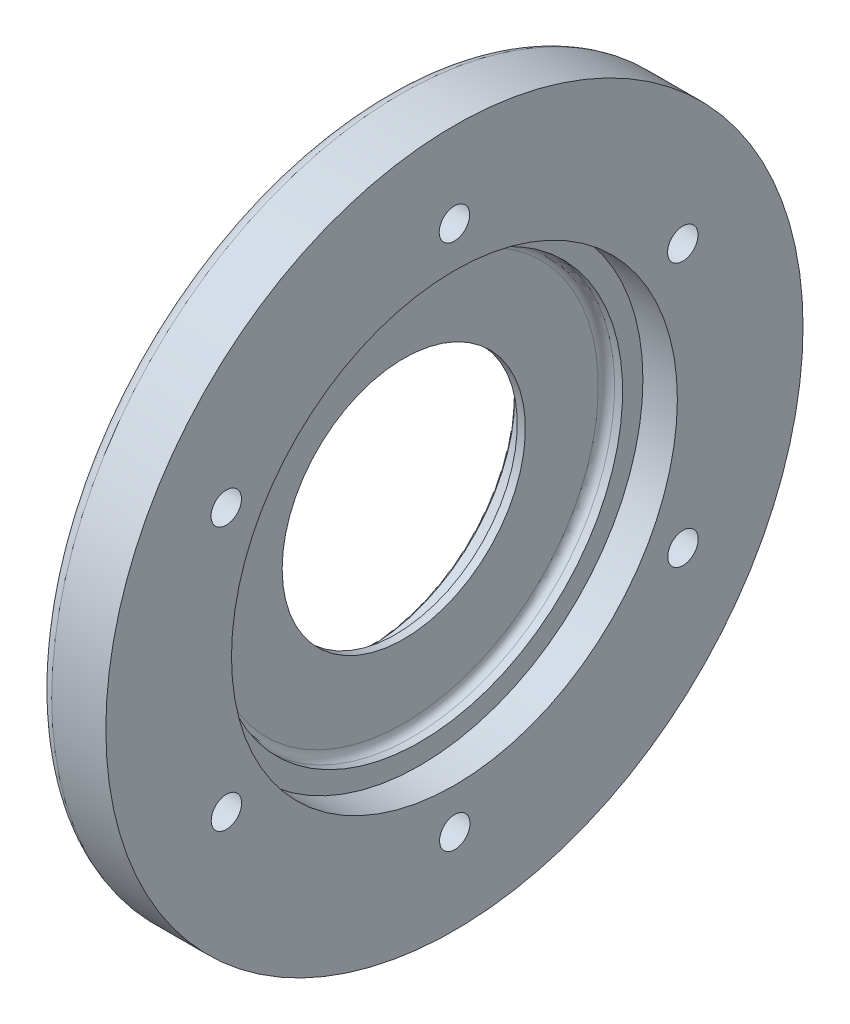
SolidWorks part; units mm, degrees
ref_plane "Front Plane" through (0, 0, 0) normal (0, 0, 1) x (1, 0, 0)
ref_plane "Top Plane" through (0, 0, 0) normal (0, 1, 0) x (1, 0, 0)
ref_plane "Right Plane" through (0, 0, 0) normal (1, 0, 0) x (0, 0, -1)
sketch "Sketch1" plane through (0, 0, 0) normal (0, 1, 0) x (1, 0, 0)
  line L0 (0.5952, 30) -> (2.5952, 30)
  line L1 (2.5952, 30) -> (2.5952, 48)
  line L2 (4.5952, 50) -> (6.5952, 50)
  line L3 (6.5952, 50) -> (6.5952, 55)
  line L7 (-2.2556, 86) -> (-2.2556, 49)
  line L8 (-5.2556, 46) -> (-6.4048, 46)
  line L9 (-6.4048, 46) -> (-6.4048, 36)
  line L10 (-6.4048, 36) -> (0.5952, 36)
  line L11 (0.5952, 36) -> (0.5952, 30)
  line L12 (6.5952, 55) -> (1.7444, 55)
  line L13 (1.7444, 55) -> (1.7444, 86)
  line L14 (1.7444, 86) -> (-2.2556, 86)
  line L16 (0, 0) -> (11.072, 0) construction
  arc A0 (-2.2556, 49) -> (-5.2556, 46) centre (-5.2556, 49) cw
  arc A1 (2.5952, 48) -> (4.5952, 50) centre (4.5952, 48) cw
  point P18 (-2.2556, 46)
  point P21 (2.5952, 50)
  dimension "D11" = 3
  dimension "D12" = 2
  dimension "D1" = 2
  dimension "D2" = 20
  dimension "D3" = 6
  dimension "D4" = 30
  dimension "D5" = 7
  dimension "D6" = 4
  dimension "D7" = 5
  dimension "D8" = 10
  dimension "D9" = 4
  dimension "D10" = 40
revolve "Revolve1" add sketch "Sketch1" angle 360 about L16
fillet "Fillet1" radius 0.5 1 edges at (-6.4048, 0, 36)
sketch "Sketch3" plane through (1.7444, 0, 0) normal (1, 0, 0) x (0, 0, -1)
  circle A0 centre (0, 0) radius 86 construction
  circle A1 centre (0, 0) radius 86
  circle A3 centre (0, 0) radius 56
fillet "Fillet5" radius 5 1 edges at (-2.2556, 0, 86)
sketch "Sketch12" plane through (1.7444, 0, 0) normal (1, 0, 0) x (0, 0, -1)
  circle A0 centre (0, 0) radius 55 construction
  circle A1 centre (0, 0) radius 55
  circle A2 centre (0, 0) radius 86 construction
  circle A3 centre (0, 0) radius 86
extrude "Boss-Extrude1" add sketch "Sketch12" along normal blind 13.35
hole_wizard "M14x2.0 Tapped Hole2" positions "Sketch10" profile "Sketch11" tap size "M14x2.0" standard "ANSI Metric"
sketch "Sketch10" plane through (-2.2556, 0, 0) normal (-1, 0, 0) x (0, 0, 1)
  line L0 (0, 81.101) -> (0, 49) construction
  circle A0 centre (0, 0) radius 65.0505 construction
  circle A1 centre (0, 0) radius 81.101 construction
  circle A2 centre (0, 0) radius 49 construction
  point P15 (0, 65.0505)
  point P20 (56.2917, 32.5)
  point P21 (56.2479, -32.5253)
  point P22 (-0.0875, -65)
  point P23 (-56.3791, -32.4495)
  point P24 (-56.3354, 32.5758)
cosmetic thread "Hole Thread10" parameters "D1"=10, "D2"=14
cosmetic thread "Hole Thread11" parameters "D1"=10, "D2"=14
cosmetic thread "Hole Thread12" parameters "D1"=10, "D2"=14
cosmetic thread "Hole Thread13" parameters "D1"=10, "D2"=14
cosmetic thread "Hole Thread14" parameters "D1"=10, "D2"=14
cosmetic thread "Hole Thread15" parameters "D1"=10, "D2"=14
sketch "Sketch11" plane through (-2.2556, 32.5758, -56.3354) normal (0, 1, 0) x (0, 0, 1)
  line L0 (0, 0) -> (0, 19.6052)
  line L1 (0, 19.6052) -> (6, 16)
  line L2 (6, 16) -> (6, 0)
  line L5 (6, 0) -> (0, 0)
  line L10 (0, 19.6052) -> (-6, 16) construction
  line L11 (0, -6.35) -> (0, 107.95) construction
  dimension "Tap Drill Dia." = 12
  dimension "Tap Drill Depth" = 16
  dimension "Drill Angle" = 118
